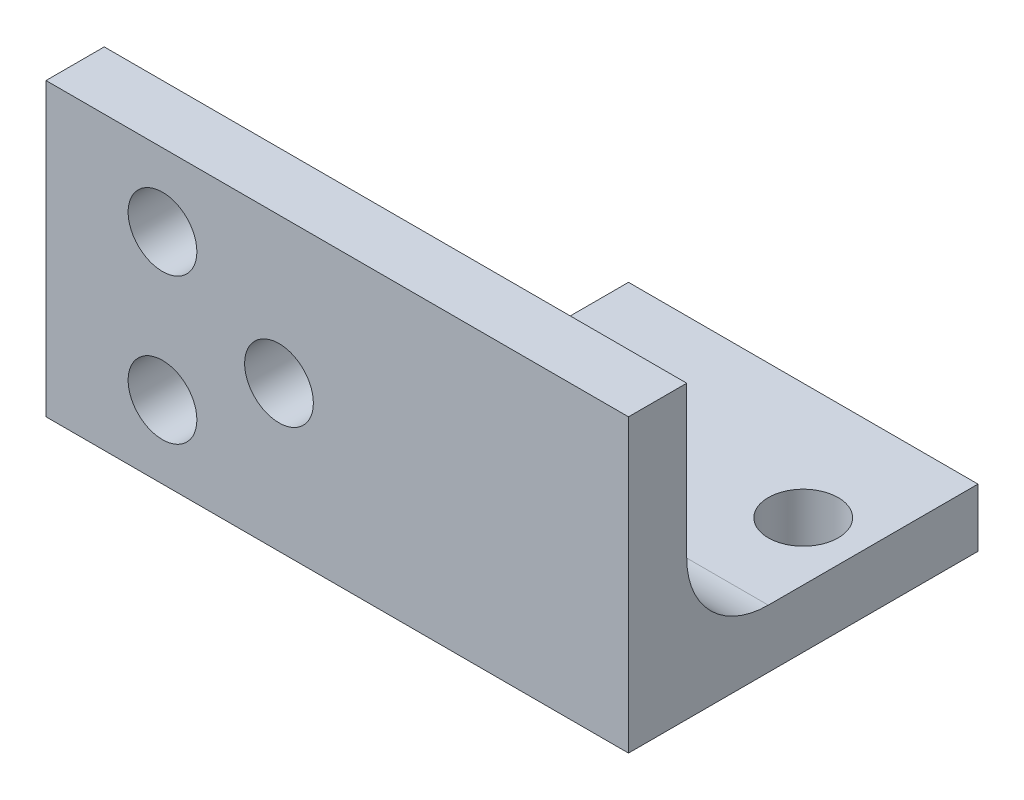
SolidWorks part; units mm, degrees
ref_plane "Alzado" through (0, 0, 0) normal (0, 0, 1) x (1, 0, 0)
ref_plane "Planta" through (0, 0, 0) normal (0, 1, 0) x (1, 0, 0)
ref_plane "Vista lateral" through (0, 0, 0) normal (1, 0, 0) x (0, 0, -1)
sketch "Croquis1" plane through (0, 0, 0) normal (0, 0, 1) x (1, 0, 0)
  line L0 (5, 25) -> (5, 0) construction
  line L1 (0, 0) -> (50, 0)
  line L2 (0, 0) -> (0, 25)
  line L3 (0, 25) -> (50, 25)
  line L4 (50, 0) -> (50, 25)
  line L5 (10, 18.75) -> (10, 6.25) construction
  circle A0 centre (10, 18.75) radius 2.95
  circle A1 centre (10, 6.25) radius 2.95
  circle A2 centre (20, 12.5) radius 2.95
  point P13 (10, 12.5)
  point P14 (0, 12.5)
  dimension "D5" = 10
  dimension "D6" = 10
  dimension "D7" = 5.9
  dimension "D1" = 50
  dimension "D2" = 25
  dimension "D3" = 5
  dimension "D4" = 12.5
extrude "Saliente-Extruir1" add sketch "Croquis1" along normal blind 5
sketch "Croquis2" plane through (0, 0, 0) normal (0, -1, 0) x (1, 0, 0)
  line L0 (50, 5) -> (50, 0) construction
  line L1 (20, 0) -> (50, 0)
  line L2 (20, 0) -> (20, -25)
  line L3 (20, -25) -> (50, -25)
  line L4 (50, 0) -> (50, -25)
  line L5 (0, 0) -> (50, 0) construction
  circle A0 centre (45, -15) radius 3
  circle A1 centre (25, -15) radius 3
  point P11 (0, 0)
  point P13 (5.1149, 0)
  dimension "D1" = 10
  dimension "D3" = 5
  dimension "D4" = 6
  dimension "D6" = 5
  dimension "D2" = 20
  dimension "D5" = 25
extrude "Saliente-Extruir2" add sketch "Croquis2" against normal blind 5
fillet "Redondeo1" radius 7 1 edges at (35, 5, 0)
